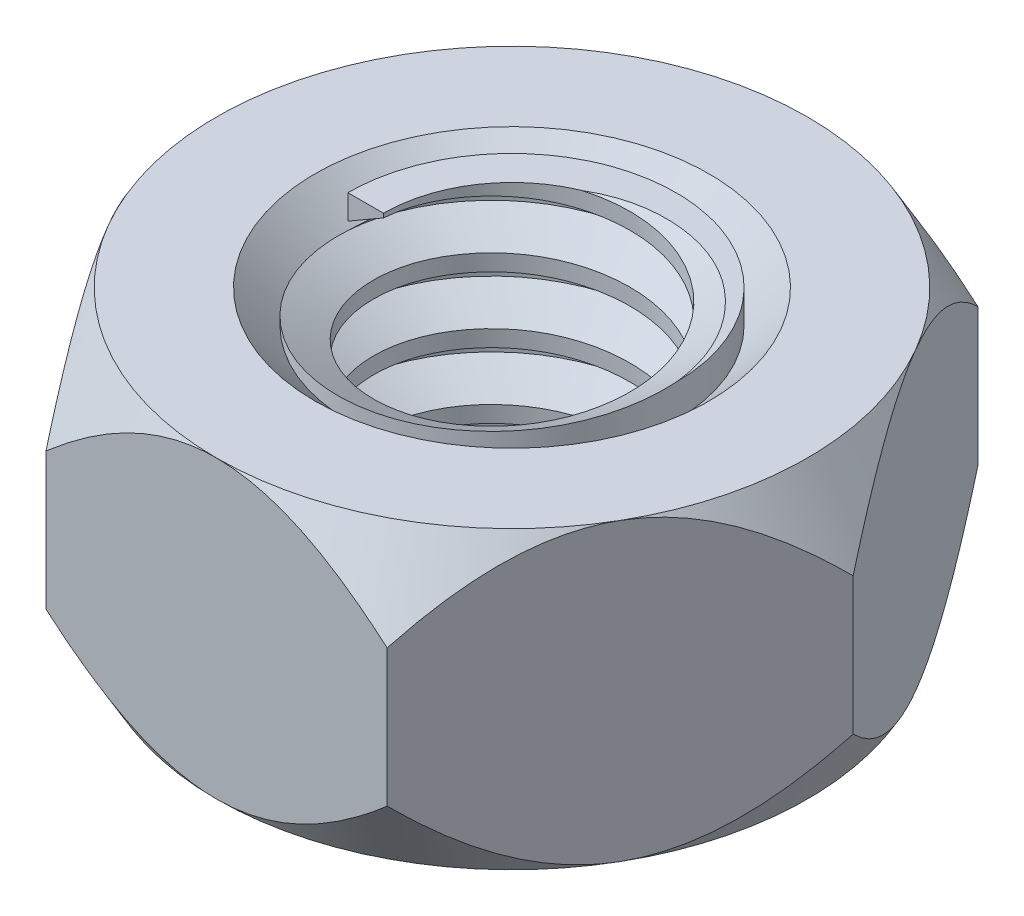
SolidWorks part; units mm, degrees
ref_plane "Front Plane" through (0, 0, 0) normal (0, 0, 1) x (1, 0, 0)
ref_plane "Top Plane" through (0, 0, 0) normal (0, 1, 0) x (1, 0, 0)
ref_plane "Right Plane" through (0, 0, 0) normal (1, 0, 0) x (0, 0, -1)
sketch "Sketch2" plane through (0, 0, 0) normal (0, 1, 0) x (1, 0, 0)
  line L1 (2.5981, 4.5) -> (-2.5981, 4.5)
  line L2 (-2.5981, 4.5) -> (-5.1962, 0)
  line L3 (-5.1962, 0) -> (-2.5981, -4.5)
  line L4 (-2.5981, -4.5) -> (2.5981, -4.5)
  line L5 (2.5981, -4.5) -> (5.1962, 0)
  line L6 (5.1962, 0) -> (2.5981, 4.5)
  circle A0 centre (0, 0) radius 2.5
  circle A1 centre (0, 0) radius 4.5 construction
  dimension "D1" = 5
  dimension "D2" = 9
extrude "Boss-Extrude1" add sketch "Sketch2" along normal mid plane 4.5
sketch "Sketch3" plane through (0, 2.25, 0) normal (0, 1, 0) x (1, 0, 0)
  circle A0 centre (0, 0) radius 4.5
  dimension "D1" = 9
extrude "Cut-Extrude1" cut sketch "Sketch3" against normal blind 4.5 draft 30 flip side to cut
mirror "Mirror1" about plane through (0, 0, 0) normal (0, 1, 0) of "Cut-Extrude1"
chamfer "Chamfer1" distance 0.5 angle 45 1 edges at (0, 2.25, 2.5)
chamfer "Chamfer2" distance 0.5 angle 45 1 edges at (0, -2.25, 2.5)
thread "Thread1" pitch 1 method extrude profile "Thread Profile1" start angle 0, offset 1, length 0, pitch 1, diameter 5
ref_plane "Plane1" through (-2.5, 2.75, 0) normal (0, 0, 1) x (-1, 0, 0)
sketch "Thread Profile1" plane through (-2.5, 2.75, 0) normal (0, 0, 1) x (-1, 0, 0)
  line L0 (0, 0) -> (0, 1) construction
  line L11 (0, 0) -> (0, 0.875)
  line L12 (0, 0.875) -> (-0.5413, 0.5625)
  line L13 (-0.5413, 0.5625) -> (-0.5413, 0.3125)
  line L15 (-0.5413, 0.3125) -> (0, 0)
  line L17 (-0.5413, 0.4375) -> (0, 0.4375) construction
  point P2 (0, 0)
  dimension "Pitch" = 1
  dimension "Profile_Angle" = 60
  dimension "Profile_Land" = 0.25
  dimension "Profile_Height" = 0.5413
ref_plane "Plane2" through (0, 2.25, 0) normal (0, 1, 0) x (1, 0, 0)
ref_plane "Plane3" through (0, -2.25, 0) normal (0, 1, 0) x (1, 0, 0)
other "SurfaceCut1"
other "SurfaceCut2" flip cut yes
